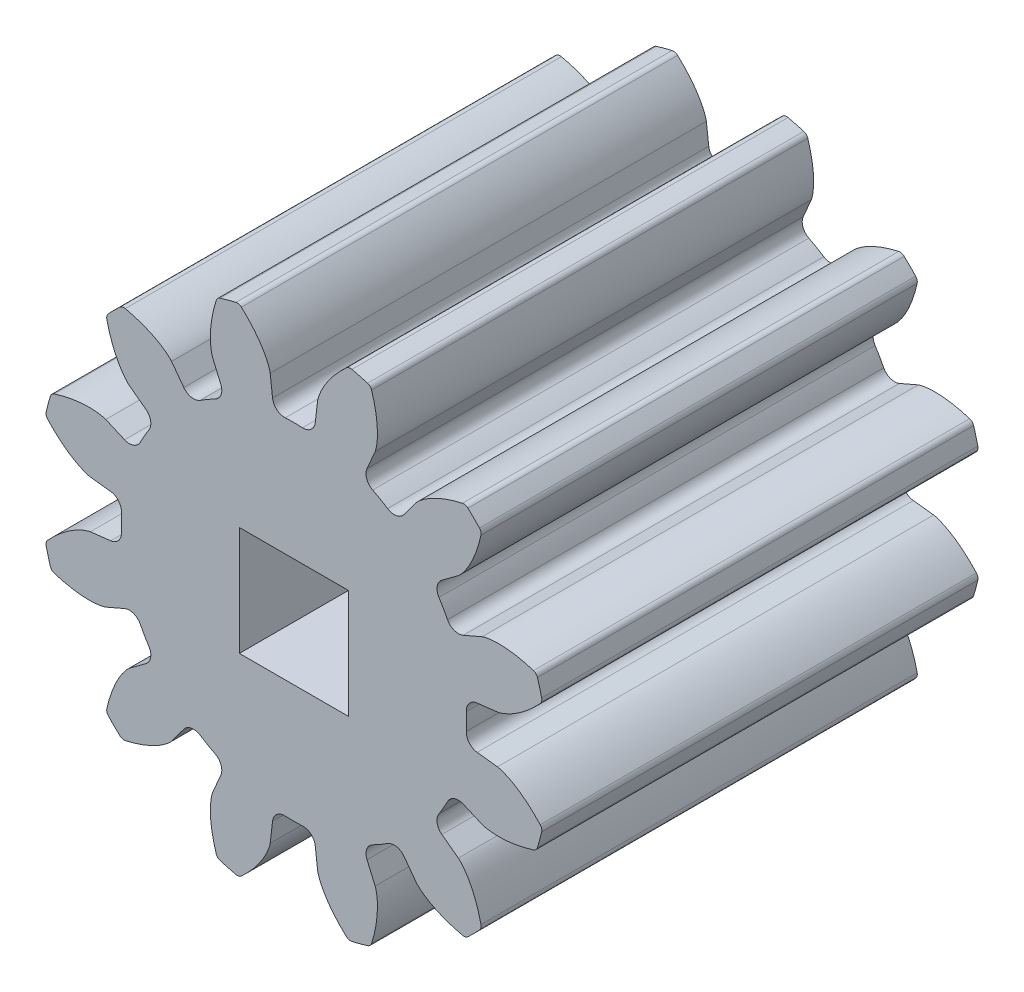
SolidWorks part; units mm, degrees
material "Alloy Steel"
ref_plane "Front" through (0, 0, 0) normal (0, 0, 1) x (1, 0, 0)
ref_plane "Top" through (0, 0, 0) normal (0, 1, 0) x (1, 0, 0)
ref_plane "Right" through (0, 0, 0) normal (1, 0, 0) x (0, 0, -1)
sketch "Sketch1" plane through (0, 0, 0) normal (0, 0, 1) x (1, 0, 0)
  circle A0 centre (0, 0) radius 7.4083
  dimension "OutsideDiameter" = 14.8167
extrude "Boss-Extrude1" add sketch "Sketch1" along normal blind 12.7
sketch "Sketch3" plane through (0, 0, 0) normal (0, 0, 1) x (1, 0, 0)
  line L0 (0, 0) -> (43.7181, 0) construction
  line L2 (0, 0) -> (-0.5818, 4.9933) construction
  line L3 (0, 0) -> (0.5818, 4.9933) construction
  line L4 (0.5818, 4.9933) -> (0.6906, 5.927) construction
  line L5 (0, 0) -> (0, 61.276) construction
  line L6 (-0.5818, 4.9933) -> (-0.6906, 5.927) construction
  circle A0 centre (0, 0) radius 7.4083 construction
  circle A1 centre (0, 0) radius 6.35 construction
  circle A2 centre (0, 0) radius 5.967 construction
  arc A3 (0.5818, 4.9933) -> (-0.5818, 4.9933) centre (0, 0) ccw construction
  arc A5 (1.5983, 7.2339) -> (-1.5983, 7.2339) centre (0, 0) ccw
  spline S0 degree 4 poles (-0.6906, 5.927) (-0.6909, 5.9293) (-0.6919, 5.9359) (-0.6942, 5.9484) (-0.6987, 5.9686) (-0.7052, 5.9942) (-0.7148, 6.0271) (-0.7275, 6.0655) (-0.7428, 6.1073) (-0.761, 6.1523) (-0.7804, 6.1969) (-0.8011, 6.2409) (-0.8228, 6.2844) (-0.8503, 6.3367) (-0.8852, 6.3986) (-0.9285, 6.47) (-0.9807, 6.5497) (-1.0371, 6.6294) (-1.0952, 6.7066) (-1.1568, 6.7832) (-1.2185, 6.8562) (-1.2856, 6.9304) (-1.3489, 6.9981) (-1.4232, 7.0721) (-1.484, 7.1312) (-1.5675, 7.2071) (-1.6179, 7.2513) (-1.6779, 7.3023) (-1.7051, 7.3245) (-1.7219, 7.3382) knots 0 0 0 0 0 0.005377 0.015084 0.028532 0.04661 0.064855 0.092111 0.119476 0.146842 0.174209 0.201575 0.228941 0.256307 0.307035 0.361767 0.4165 0.471232 0.525964 0.580697 0.635429 0.690161 0.744894 0.799626 0.854358 0.909091 0.954545 1 1 1 1 1 construction
  spline S1 degree 4 poles (-0.6906, 5.927) (-0.6909, 5.9293) (-0.6919, 5.9359) (-0.6942, 5.9484) (-0.6987, 5.9686) (-0.7052, 5.9942) (-0.7148, 6.0271) (-0.7275, 6.0655) (-0.7428, 6.1073) (-0.761, 6.1523) (-0.7804, 6.1969) (-0.8011, 6.2409) (-0.8228, 6.2844) (-0.8503, 6.3367) (-0.8852, 6.3986) (-0.9285, 6.47) (-0.9807, 6.5497) (-1.0371, 6.6294) (-1.0952, 6.7066) (-1.1568, 6.7832) (-1.2185, 6.8562) (-1.2856, 6.9304) (-1.3489, 6.9981) (-1.4232, 7.0721) (-1.484, 7.1312) (-1.5494, 7.1906) (-1.5816, 7.2193) (-1.5983, 7.2339) knots 0 0 0 0 0 0.005377 0.015084 0.028532 0.04661 0.064855 0.092111 0.119476 0.146842 0.174209 0.201575 0.228941 0.256307 0.307035 0.361767 0.4165 0.471232 0.525964 0.580697 0.635429 0.690161 0.744894 0.799626 0.854358 0.909091 0.909091 0.909091 0.909091 0.909091
  spline S2 degree 4 poles (0.6906, 5.927) (0.6909, 5.9293) (0.6919, 5.9359) (0.6942, 5.9484) (0.6987, 5.9686) (0.7052, 5.9942) (0.7148, 6.0271) (0.7275, 6.0655) (0.7428, 6.1073) (0.761, 6.1523) (0.7804, 6.1969) (0.8011, 6.2409) (0.8228, 6.2844) (0.8503, 6.3367) (0.8852, 6.3986) (0.9285, 6.47) (0.9807, 6.5497) (1.0371, 6.6294) (1.0952, 6.7066) (1.1568, 6.7832) (1.2185, 6.8562) (1.2856, 6.9304) (1.3489, 6.9981) (1.4232, 7.0721) (1.484, 7.1312) (1.5675, 7.2071) (1.6179, 7.2513) (1.6779, 7.3023) (1.7051, 7.3245) (1.7219, 7.3382) knots 0 0 0 0 0 0.005377 0.015084 0.028532 0.04661 0.064855 0.092111 0.119476 0.146842 0.174209 0.201575 0.228941 0.256307 0.307035 0.361767 0.4165 0.471232 0.525964 0.580697 0.635429 0.690161 0.744894 0.799626 0.854358 0.909091 0.954545 1 1 1 1 1 construction
  spline S3 degree 4 poles (0.6906, 5.927) (0.6909, 5.9293) (0.6919, 5.9359) (0.6942, 5.9484) (0.6987, 5.9686) (0.7052, 5.9942) (0.7148, 6.0271) (0.7275, 6.0655) (0.7428, 6.1073) (0.761, 6.1523) (0.7804, 6.1969) (0.8011, 6.2409) (0.8228, 6.2844) (0.8503, 6.3367) (0.8852, 6.3986) (0.9285, 6.47) (0.9807, 6.5497) (1.0371, 6.6294) (1.0952, 6.7066) (1.1568, 6.7832) (1.2185, 6.8562) (1.2856, 6.9304) (1.3489, 6.9981) (1.4232, 7.0721) (1.484, 7.1312) (1.5494, 7.1906) (1.5816, 7.2193) (1.5983, 7.2339) knots 0 0 0 0 0 0.005377 0.015084 0.028532 0.04661 0.064855 0.092111 0.119476 0.146842 0.174209 0.201575 0.228941 0.256307 0.307035 0.361767 0.4165 0.471232 0.525964 0.580697 0.635429 0.690161 0.744894 0.799626 0.854358 0.909091 0.909091 0.909091 0.909091 0.909091
  point P0 (0, 5.0271)
  dimension "OutsideDiameter" = 14.8167
  dimension "PitchCircle" = 12.7
  dimension "BaseCircle" = 11.9341
  dimension "DedendumCircle" = 10.0542
sketch "DCLTBC" plane through (0, 0, 0) normal (0, 0, 1) x (1, 0, 0)
  line L0 (0, 0) -> (41.04, 0) construction
  line L1 (-0.5818, 4.9933) -> (-0.6906, 5.927) construction
  line L2 (0.5818, 4.9933) -> (0.6906, 5.927) construction
  line L3 (-0.5818, 4.9933) -> (-0.6906, 5.927)
  line L4 (0.5818, 4.9933) -> (0.6906, 5.927)
  line L5 (0, 0) -> (0, 104.9356) construction
  circle A0 centre (0, 0) radius 7.4083
  circle A1 centre (0, 0) radius 6.35 construction
  circle A2 centre (0, 0) radius 5.967 construction
  arc A3 (0.5818, 4.9933) -> (-0.5818, 4.9933) centre (0, 0) ccw construction
  arc A4 (0.5818, 4.9933) -> (-0.5818, 4.9933) centre (0, 0) ccw
  spline S0 degree 4 poles (-992.2327, -123.7493) (-11.7184, 3.7577) (-0.7821, 5.3359) (-0.6334, 5.6707) (-0.6987, 5.9686) (-0.7052, 5.9942) (-0.7148, 6.0271) (-0.7275, 6.0655) (-0.7428, 6.1073) (-0.761, 6.1523) (-0.7804, 6.1969) (-0.8011, 6.2409) (-0.8228, 6.2844) (-0.8503, 6.3367) (-0.8852, 6.3986) (-0.9285, 6.47) (-0.9807, 6.5497) (-1.0371, 6.6294) (-1.0952, 6.7066) (-1.1568, 6.7832) (-1.2185, 6.8562) (-1.2856, 6.9304) (-1.3489, 6.9981) (-1.4232, 7.0721) (-1.7629, 7.4024) (-3.091, 8.4823) (16.0015, -8.3782) (-754.2601, 665.5952) knots -0.639841 -0.639841 -0.639841 -0.639841 -0.639841 0.005377 0.015084 0.028532 0.04661 0.064855 0.092111 0.119476 0.146842 0.174209 0.201575 0.228941 0.256307 0.307035 0.361767 0.4165 0.471232 0.525964 0.580697 0.635429 0.690161 0.744894 0.799626 0.854358 1.913215 1.913215 1.913215 1.913215 1.913215 only from (-0.6906, 5.927) to (-1.5983, 7.2339) construction
  spline S1 degree 4 poles (992.2327, -123.7493) (11.7184, 3.7577) (0.7821, 5.3359) (0.6334, 5.6707) (0.6987, 5.9686) (0.7052, 5.9942) (0.7148, 6.0271) (0.7275, 6.0655) (0.7428, 6.1073) (0.761, 6.1523) (0.7804, 6.1969) (0.8011, 6.2409) (0.8228, 6.2844) (0.8503, 6.3367) (0.8852, 6.3986) (0.9285, 6.47) (0.9807, 6.5497) (1.0371, 6.6294) (1.0952, 6.7066) (1.1568, 6.7832) (1.2185, 6.8562) (1.2856, 6.9304) (1.3489, 6.9981) (1.4232, 7.0721) (1.7629, 7.4024) (3.091, 8.4823) (-16.0015, -8.3782) (754.2601, 665.5952) knots -0.639841 -0.639841 -0.639841 -0.639841 -0.639841 0.005377 0.015084 0.028532 0.04661 0.064855 0.092111 0.119476 0.146842 0.174209 0.201575 0.228941 0.256307 0.307035 0.361767 0.4165 0.471232 0.525964 0.580697 0.635429 0.690161 0.744894 0.799626 0.854358 1.913215 1.913215 1.913215 1.913215 1.913215 only from (0.6906, 5.927) to (1.5983, 7.2339) construction
  spline S2 degree 4 poles (-0.6906, 5.927) (-0.6909, 5.9293) (-0.6919, 5.9359) (-0.6942, 5.9484) (-0.6987, 5.9686) (-0.7052, 5.9942) (-0.7148, 6.0271) (-0.7275, 6.0655) (-0.7428, 6.1073) (-0.761, 6.1523) (-0.7804, 6.1969) (-0.8011, 6.2409) (-0.8228, 6.2844) (-0.8503, 6.3367) (-0.8852, 6.3986) (-0.9285, 6.47) (-0.9807, 6.5497) (-1.0371, 6.6294) (-1.0952, 6.7066) (-1.1568, 6.7832) (-1.2185, 6.8562) (-1.2856, 6.9304) (-1.3489, 6.9981) (-1.4232, 7.0721) (-1.484, 7.1312) (-1.5494, 7.1906) (-1.5816, 7.2193) (-1.5983, 7.2339) knots 0 0 0 0 0 0.005377 0.015084 0.028532 0.04661 0.064855 0.092111 0.119476 0.146842 0.174209 0.201575 0.228941 0.256307 0.307035 0.361767 0.4165 0.471232 0.525964 0.580697 0.635429 0.690161 0.744894 0.799626 0.854358 0.909091 0.909091 0.909091 0.909091 0.909091
  spline S3 degree 4 poles (0.6906, 5.927) (0.6909, 5.9293) (0.6919, 5.9359) (0.6942, 5.9484) (0.6987, 5.9686) (0.7052, 5.9942) (0.7148, 6.0271) (0.7275, 6.0655) (0.7428, 6.1073) (0.761, 6.1523) (0.7804, 6.1969) (0.8011, 6.2409) (0.8228, 6.2844) (0.8503, 6.3367) (0.8852, 6.3986) (0.9285, 6.47) (0.9807, 6.5497) (1.0371, 6.6294) (1.0952, 6.7066) (1.1568, 6.7832) (1.2185, 6.8562) (1.2856, 6.9304) (1.3489, 6.9981) (1.4232, 7.0721) (1.484, 7.1312) (1.5494, 7.1906) (1.5816, 7.2193) (1.5983, 7.2339) knots 0 0 0 0 0 0.005377 0.015084 0.028532 0.04661 0.064855 0.092111 0.119476 0.146842 0.174209 0.201575 0.228941 0.256307 0.307035 0.361767 0.4165 0.471232 0.525964 0.580697 0.635429 0.690161 0.744894 0.799626 0.854358 0.909091 0.909091 0.909091 0.909091 0.909091
  dimension "OutsideDiameter" = 14.8167
  dimension "PitchCircle" = 12.7
  dimension "BaseCircle" = 11.9341
extrude "Cut-Extrude-DCLTBC" cut sketch "DCLTBC" along normal through all contours L4 S3 A0 S2 L3 A4 region at (0, 6.4063, 0)
fillet "Fillet-Tip-DCLTBC" radius 0.1775 2 edges at (1.5983, 7.2339, 6.35) (-1.5983, 7.2339, 6.35)
fillet "Fillet-Root-DCLTBC" radius 0.3551 2 edges at (-0.5818, 4.9933, 6.35) (0.5818, 4.9933, 6.35)
pattern_circular "CirPattern-DCLTBC" count 12 over 360 about axis through (0, 0, 12.7) along (0, 0, 1) of "Cut-Extrude-DCLTBC", "Fillet-Tip-DCLTBC", "Fillet-Root-DCLTBC"
sketch "DCGTBC" [suppressed] plane through (0, 0, 0) normal (0, 0, 1) x (1, 0, 0)
  line L0 (0, 0) -> (41.04, 0) construction
  line L1 (-33.4742, 2.9286) -> (0, 0) construction
  line L2 (0, 0) -> (33.4742, 2.9286) construction
  line L3 (0, 0) -> (-16.5124, 0)
  line L5 (0, 0) -> (0, 104.9356) construction
  circle A0 centre (0, 0) radius 35.9833
  circle A1 centre (0, 0) radius 34.925 construction
  circle A2 centre (0, 0) radius 32.8188 construction
  arc A3 (0.2989, 33.6008) -> (-0.2989, 33.6008) centre (0, 0) ccw construction
  arc A11 (33.4742, 2.9286) -> (-33.4742, 2.9286) centre (0, 0) ccw
  spline S4 degree 4 poles (999.6179, -3.7707) (12.1623, 31.0827) (0.4581, 31.7209) (0.2553, 32.3127) (0.2967, 32.9045) (0.3017, 32.9586) (0.3095, 33.0284) (0.3204, 33.1106) (0.3343, 33.201) (0.3514, 33.2993) (0.3703, 33.3974) (0.3907, 33.4951) (0.4126, 33.5925) (0.4408, 33.7105) (0.477, 33.8518) (0.523, 34.017) (0.5794, 34.2042) (0.6413, 34.395) (0.706, 34.5826) (0.7756, 34.772) (0.846, 34.9552) (0.9235, 35.1454) (0.9973, 35.3209) (1.0848, 35.5175) (1.4313, 36.2799) (2.6636, 38.6565) (-10.9768, 10.7922) (444.1484, 932.5353) knots -0.603811 -0.603811 -0.603811 -0.603811 -0.603811 0.005377 0.015084 0.028532 0.04661 0.064855 0.092111 0.119476 0.146842 0.174209 0.201575 0.228941 0.256307 0.307035 0.361767 0.4165 0.471232 0.525964 0.580697 0.635429 0.690161 0.744894 0.799626 0.854358 1.742885 1.742885 1.742885 1.742885 1.742885 only from (0.2919, 32.8175) to (1.2943, 35.96) construction
  spline S5 degree 4 poles (-999.6179, -3.7707) (-12.1623, 31.0827) (-0.4581, 31.7209) (-0.2553, 32.3127) (-0.2967, 32.9045) (-0.3017, 32.9586) (-0.3095, 33.0284) (-0.3204, 33.1106) (-0.3343, 33.201) (-0.3514, 33.2993) (-0.3703, 33.3974) (-0.3907, 33.4951) (-0.4126, 33.5925) (-0.4408, 33.7105) (-0.477, 33.8518) (-0.523, 34.017) (-0.5794, 34.2042) (-0.6413, 34.395) (-0.706, 34.5826) (-0.7756, 34.772) (-0.846, 34.9552) (-0.9235, 35.1454) (-0.9973, 35.3209) (-1.0848, 35.5175) (-1.4313, 36.2799) (-2.6636, 38.6565) (10.9768, 10.7922) (-444.1484, 932.5353) knots -0.603811 -0.603811 -0.603811 -0.603811 -0.603811 0.005377 0.015084 0.028532 0.04661 0.064855 0.092111 0.119476 0.146842 0.174209 0.201575 0.228941 0.256307 0.307035 0.361767 0.4165 0.471232 0.525964 0.580697 0.635429 0.690161 0.744894 0.799626 0.854358 1.742885 1.742885 1.742885 1.742885 1.742885 only from (-0.2919, 32.8175) to (-1.2943, 35.96) construction
  spline S6 degree 4 poles (0.2919, 32.8175) (0.292, 32.8224) (0.2924, 32.8361) (0.2937, 32.8621) (0.2967, 32.9045) (0.3017, 32.9586) (0.3095, 33.0284) (0.3204, 33.1106) (0.3343, 33.201) (0.3514, 33.2993) (0.3703, 33.3974) (0.3907, 33.4951) (0.4126, 33.5925) (0.4408, 33.7105) (0.477, 33.8518) (0.523, 34.017) (0.5794, 34.2042) (0.6413, 34.395) (0.706, 34.5826) (0.7756, 34.772) (0.846, 34.9552) (0.9235, 35.1454) (0.9973, 35.3209) (1.0848, 35.5175) (1.1568, 35.676) (1.2354, 35.8397) (1.2742, 35.9193) (1.2943, 35.96) knots 0 0 0 0 0 0.005377 0.015084 0.028532 0.04661 0.064855 0.092111 0.119476 0.146842 0.174209 0.201575 0.228941 0.256307 0.307035 0.361767 0.4165 0.471232 0.525964 0.580697 0.635429 0.690161 0.744894 0.799626 0.854358 0.909091 0.909091 0.909091 0.909091 0.909091
  spline S7 degree 4 poles (-0.2919, 32.8175) (-0.292, 32.8224) (-0.2924, 32.8361) (-0.2937, 32.8621) (-0.2967, 32.9045) (-0.3017, 32.9586) (-0.3095, 33.0284) (-0.3204, 33.1106) (-0.3343, 33.201) (-0.3514, 33.2993) (-0.3703, 33.3974) (-0.3907, 33.4951) (-0.4126, 33.5925) (-0.4408, 33.7105) (-0.477, 33.8518) (-0.523, 34.017) (-0.5794, 34.2042) (-0.6413, 34.395) (-0.706, 34.5826) (-0.7756, 34.772) (-0.846, 34.9552) (-0.9235, 35.1454) (-0.9973, 35.3209) (-1.0848, 35.5175) (-1.1568, 35.676) (-1.2354, 35.8397) (-1.2742, 35.9193) (-1.2943, 35.96) knots 0 0 0 0 0 0.005377 0.015084 0.028532 0.04661 0.064855 0.092111 0.119476 0.146842 0.174209 0.201575 0.228941 0.256307 0.307035 0.361767 0.4165 0.471232 0.525964 0.580697 0.635429 0.690161 0.744894 0.799626 0.854358 0.909091 0.909091 0.909091 0.909091 0.909091
  dimension "D1" = 5
  dimension "D2" = 5
  dimension "OutsideDiameter" = 14.8167
  dimension "PitchCircle" = 12.7
  dimension "BaseCircle" = 11.9341
extrude "Cut-Extrude-DCGTBC" [suppressed] cut sketch "DCGTBC" along normal through all
fillet "Fillet-Tip-DCGTBC" [suppressed] radius 0.1775
pattern_circular "CirPattern-DCGTBC" [suppressed] count 12 over 360 of bodies 112
sketch "Sketch4" plane through (0, 0, 12.7) normal (0, 0, 1) x (1, 0, 0)
  line L1 (-1.5875, -1.5875) -> (1.5875, -1.5875)
  line L2 (-1.5875, -1.5875) -> (-1.5875, 1.5875)
  line L3 (-1.5875, 1.5875) -> (1.5875, 1.5875)
  line L4 (1.5875, -1.5875) -> (1.5875, 1.5875)
  line L5 (-1.5875, -1.5875) -> (1.5875, 1.5875) construction
  line L6 (-1.5875, 1.5875) -> (1.5875, -1.5875) construction
  point P0 (0, 0)
  dimension "D1" = 3.175
extrude "Cut-Extrude2" cut sketch "Sketch4" against normal through all
equation "\"DiametralPitch\"= 24'Diametral Pitch"
equation "\"NumTeeth\"= 12'Number of Teeth"
equation "\"PressureAngle\"= 20deg'Pressure Angle"
equation "\"Addendum\"= 1 / \"DiametralPitch\"'Addendum"
equation "\"Dedendum\"= 1.25 / \"DiametralPitch\"'Dedendum"
equation "\"WorkingDepth\"= 2 / \"DiametralPitch\"'Working Depth - here for REF (Not used in building model)"
equation "\"WholeDepth\"= 2.25 / \"DiametralPitch\"'Whole Depth - here for REF (Not used in building model)"
equation "\"Clearance\"= .25 / \"DiametralPitch\"'Clearance"
equation "\"CircularPitch\"= pi / \"DiametralPitch\"'Circular Pitch - here for REF (Not used in building model)"
equation "\"PitchCircle\"= \"NumTeeth\" / \"DiametralPitch\"'Pitch Circle - or - Pitch Diameter"
equation "\"OutsideDiameter\"= ( \"NumTeeth\" + 2 ) / \"DiametralPitch\"'Outside Diameter"
equation "\"Fillet_Root\"= \"Clearance\" * cos ( \"PressureAngle\" ) * tan ( ( 90 + \"PressureAngle\" ) / 2 ) 'Fillet Root"
equation "\"AddendumCircle\"= \"PitchCircle\" + ( 2 * \"Addendum\" )'Addendum Circle - or - Addendum Diameter"
equation "\"DedendumCircle\"= \"PitchCircle\" - ( 2 * \"Dedendum\" )'Dedendum Circle - or - Dedendum Diameter"
equation "\"BaseCircle\"= \"PitchCircle\" * cos ( \"PressureAngle\" )'Base Circle - Base Diameter"
equation "\"PitchAngle\"= 360deg / \"NumTeeth\"'Pitch Angle"
equation "\"Alpha\"= sqr ( \"PitchCircle\" ^ 2 - \"BaseCircle\" ^ 2 ) / \"BaseCircle\" * 180 / PI - \"PressureAngle\"'Alpha - Used for Calculating Beta"
equation "\"Beta\"= ( \"PitchAngle\" / 4 - ( \"Alpha\" - 90 ) )'Beta - Used in definition of the parameters for the parametric equation driven curve"
equation "\"Gamma\"= ( \"PitchAngle\" / 4 - ( \"Alpha\" + 90 ) )'Gamma - Used in definition of the parameters for the parametric equation driven curve"
equation "\"Phi\"= sqr ( ( \"AddendumCircle\" / 2 ) ^ 2 - ( \"BaseCircle\" / 2 ) ^ 2 ) / ( \"BaseCircle\" / 2 )'Phi - Used in definition of the parameters for the parametric equation driven curve"
equation "\"DCGTBC\"= iif ( \"DedendumCircle\" > \"BaseCircle\" , \"unsuppressed\" , \"suppressed\" )'if Dedendum Circle IS GREATER THAN BaseCircle THEN UnsuppressORSuppress FEATURE"
equation "\"DCLTBC\"= iif ( \"DedendumCircle\" - .002 > \"BaseCircle\" , \"suppressed\" , \"unsuppressed\" )'if Dedendum Circle - .002 IS GREATER THAN BaseCircle THEN SuppressORUnsuppress FEATURE"
equation "\"Cut-Extrude-DCGTBC\"= iif ( \"DedendumCircle\" > \"BaseCircle\" , \"unsuppressed\" , \"suppressed\" )'if Dedendum Circle IS GREATER THAN BaseCircle THEN UnsuppressORSuppress FEATURE"
equation "\"Cut-Extrude-DCLTBC\"= iif ( \"DedendumCircle\" - .002 > \"BaseCircle\" , \"suppressed\" , \"unsuppressed\" )'if Dedendum Circle - .002 IS GREATER THAN BaseCircle THEN SuppressORUnsuppress FEATURE"
equation "\"CirPattern-DCGTBC\"= iif ( \"DedendumCircle\" > \"BaseCircle\" , \"unsuppressed\" , \"suppressed\" )'if Dedendum Circle IS GREATER THAN BaseCircle THEN UnsuppressORSuppress FEATURE"
equation "\"CirPattern-DCLTBC\"= iif ( \"DedendumCircle\" - .002 > \"BaseCircle\" , \"suppressed\" , \"unsuppressed\" )'if Dedendum Circle - .002 IS GREATER THAN BaseCircle THEN SuppressORUnsuppress FEATURE"
equation "\"Fillet-Tip-DCGTBC\"= iif ( \"DedendumCircle\" > \"BaseCircle\" , \"unsuppressed\" , \"suppressed\" )'if Dedendum Circle IS GREATER THAN BaseCircle THEN UnsuppressORSuppress FEATURE"
equation "\"Fillet-Tip-DCLTBC\"= iif ( \"DedendumCircle\" - .002 > \"BaseCircle\" , \"suppressed\" , \"unsuppressed\" )'if Dedendum Circle - .002 IS GREATER THAN BaseCircle THEN SuppressORUnsuppress FEATURE"
equation "\"Fillet-Root-DCLTBC\"= iif ( \"DedendumCircle\" - .002 > \"BaseCircle\" , \"suppressed\" , \"unsuppressed\" )'if Dedendum Circle - .002 IS GREATER THAN BaseCircle THEN SuppressORUnsuppress FEATURE"
equation "\"D1@CirPattern-DCGTBC\"= \"NumTeeth\"'Number of Teeth"
equation "\"D1@CirPattern-DCLTBC\"= \"NumTeeth\"'Number of Teeth"
equation "\"D1@Fillet-Tip-DCGTBC\"= \"Fillet_Root\" / 2 'Tip Rad For Large No of Teeth"
equation "\"D1@Fillet-Tip-DCLTBC\"=\"Fillet_Root\" / 2'Tip Rad For Small No of Teeth"
equation "\"D1@Fillet-Root-DCLTBC\"= \"Fillet_Root\"'Fillet Root"
